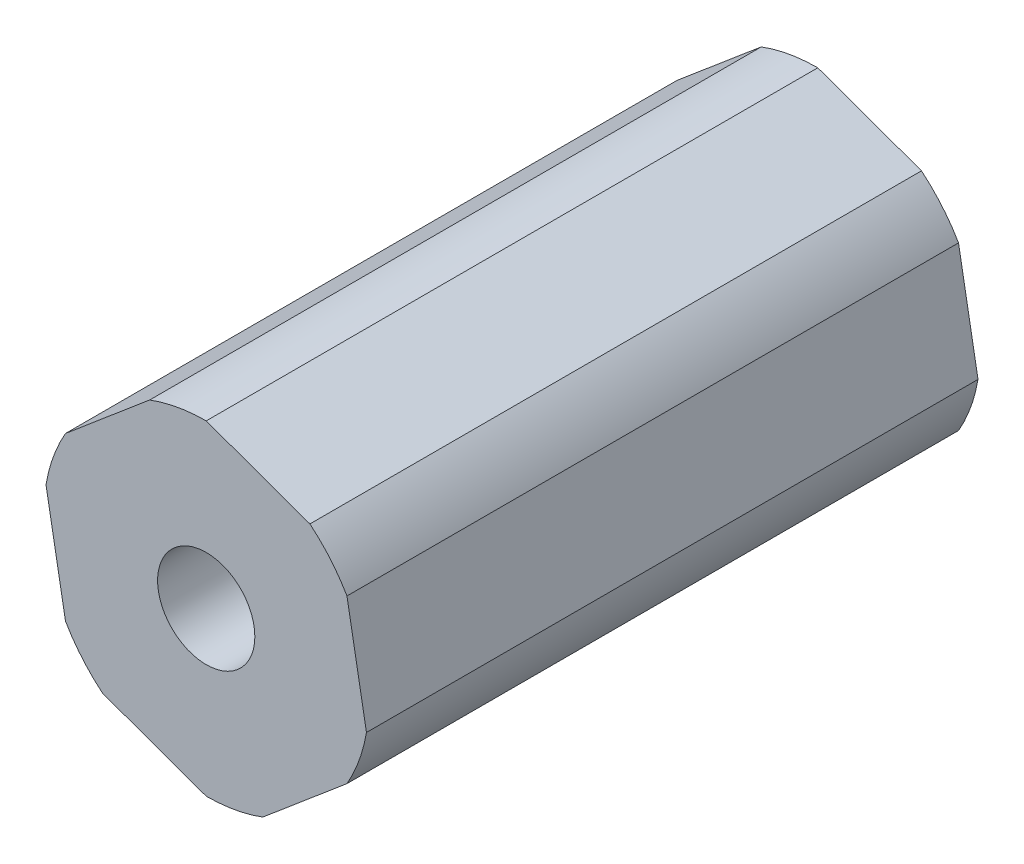
SolidWorks part; units mm, degrees
material "7075-T6 (SN)"
ref_plane "Front Plane" through (0, 0, 0) normal (0, 0, 1) x (1, 0, 0)
ref_plane "Top Plane" through (0, 0, 0) normal (0, 1, 0) x (1, 0, 0)
ref_plane "Right Plane" through (0, 0, 0) normal (1, 0, 0) x (0, 0, -1)
sketch "Sketch1" plane through (0, 0, 0) normal (0, 0, 1) x (1, 0, 0)
  line L1 (-6.6545, 1.1312) -> (-5.8457, -3.375)
  line L2 (-4.3069, -5.1974) -> (0, -6.75)
  line L3 (2.3476, -6.3286) -> (5.8457, -3.375)
  line L4 (6.6545, -1.1312) -> (5.8457, 3.375)
  line L5 (4.3069, 5.1974) -> (0, 6.75)
  line L6 (-2.3476, 6.3286) -> (-5.8457, 3.375)
  circle A0 centre (0, 0) radius 6.35 construction
  arc A1 (-5.8457, 3.375) -> (-6.6545, 1.1312) centre (0, 0) ccw
  arc A2 (-5.8457, -3.375) -> (-4.3069, -5.1974) centre (0, 0) ccw
  arc A3 (0, -6.75) -> (2.3476, -6.3286) centre (0, 0) ccw
  arc A4 (5.8457, -3.375) -> (6.6545, -1.1312) centre (0, 0) ccw
  arc A5 (5.8457, 3.375) -> (4.3069, 5.1974) centre (0, 0) ccw
  arc A6 (0, 6.75) -> (-2.3476, 6.3286) centre (0, 0) ccw
  dimension "D1" = 12.7
  dimension "D2" = 13.5
extrude "Boss-Extrude1" add sketch "Sketch1" along normal blind 25.4
sketch "Sketch2" plane through (0, 0, 25.4) normal (0, 0, 1) x (1, 0, 0)
  circle A0 centre (0, 0) radius 2.0193
  dimension "D1" = 4.0386
extrude "Cut-Extrude1" cut sketch "Sketch2" against normal through all
